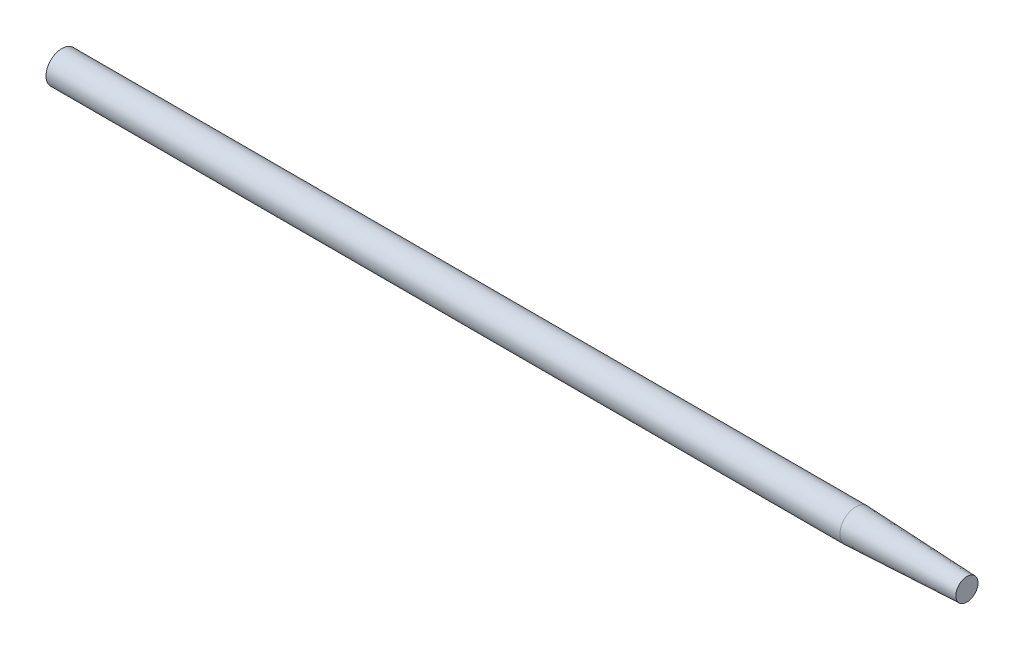
SolidWorks part; units mm, degrees
ref_plane "Ön Düzlem" through (0, 0, 0) normal (0, 0, 1) x (1, 0, 0)
ref_plane "Üst Düzlem" through (0, 0, 0) normal (0, 1, 0) x (1, 0, 0)
ref_plane "Sağ Düzlem" through (0, 0, 0) normal (1, 0, 0) x (0, 0, -1)
sketch "Çizim1" plane through (0, 0, 0) normal (0, 0, 1) x (1, 0, 0)
  line L1 (0, 0) -> (570, 0)
  line L2 (0, 0) -> (0, 10)
  line L3 (0, 10) -> (570, 10)
  line L4 (570, 0) -> (570, 10)
  dimension "D1" = 10
  dimension "D2" = 570
revolve "Döndür1" add sketch "Çizim1" angle 360 about L1
chamfer "Pah1" distance 3 distance2 70 1 edges at (570, 0, 10) first distance on face at (570, 0, 10)
